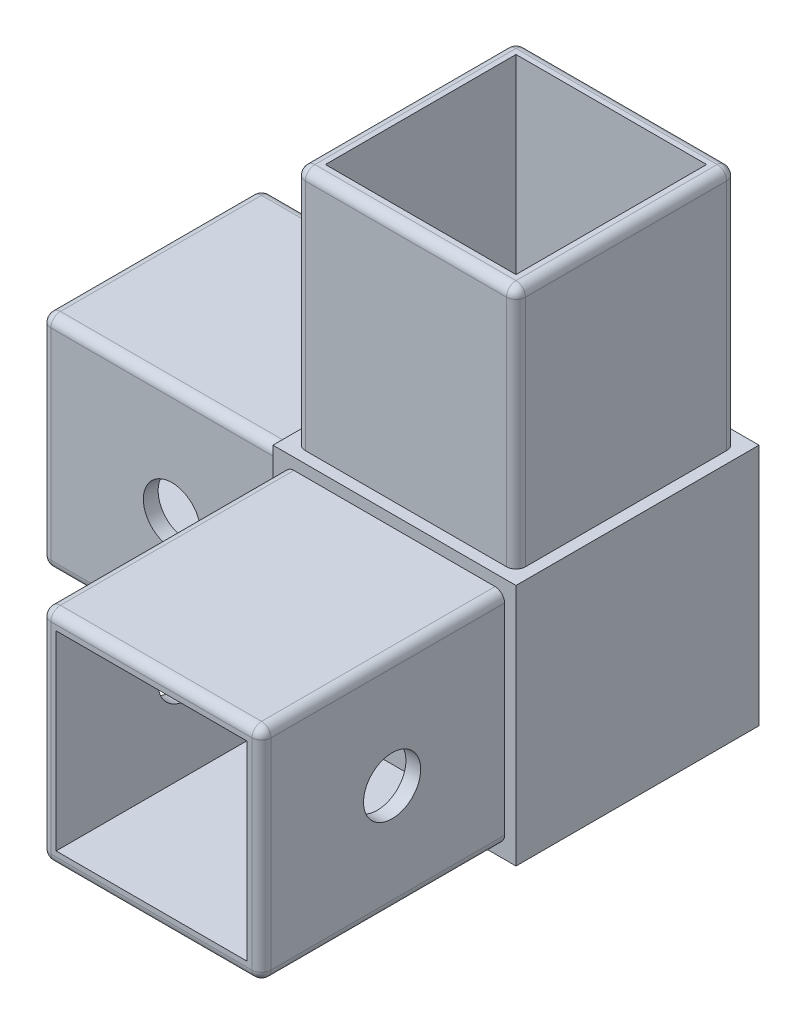
SolidWorks part; units mm, degrees
material "PBT General Purpose"
ref_plane "Front Plane" through (0, 0, 0) normal (0, 0, 1) x (1, 0, 0)
ref_plane "Top Plane" through (0, 0, 0) normal (0, 1, 0) x (1, 0, 0)
ref_plane "Right Plane" through (0, 0, 0) normal (1, 0, 0) x (0, 0, -1)
sketch "Sketch1" plane through (0, 0, 0) normal (0, 0, 1) x (1, 0, 0)
  line L1 (-12.75, -12.75) -> (12.75, -12.75)
  line L2 (-12.75, -12.75) -> (-12.75, 12.75)
  line L3 (-12.75, 12.75) -> (12.75, 12.75)
  line L4 (12.75, -12.75) -> (12.75, 12.75)
  line L5 (-12.75, -12.75) -> (12.75, 12.75) construction
  line L6 (-12.75, 12.75) -> (12.75, -12.75) construction
  point P0 (0, 0)
  dimension "D1" = 25.5
extrude "Boss-Extrude1" add sketch "Sketch1" along normal blind 25.5
sketch "Sketch2" plane through (0, 12.75, 0) normal (0, 1, 0) x (1, 0, 0)
  line L0 (0, 0) -> (0, -25.5) construction
  line L1 (12.75, -25.5) -> (-12.75, -25.5) construction
  line L3 (12.75, -25.5) -> (12.75, 0) construction
  line L4 (12.75, -12.75) -> (-12.75, -12.75) construction
  line L5 (-12.75, -25.5) -> (-12.75, 0) construction
  line L6 (-11.55, -24.3) -> (11.55, -24.3)
  line L7 (-11.55, -24.3) -> (-11.55, -1.2)
  line L8 (-11.55, -1.2) -> (11.55, -1.2)
  line L9 (11.55, -24.3) -> (11.55, -1.2)
  line L10 (-11.55, -24.3) -> (11.55, -1.2) construction
  line L11 (-11.55, -1.2) -> (11.55, -24.3) construction
  line L12 (-10, -2.75) -> (10, -2.75)
  line L13 (-10, -2.75) -> (-10, -22.75)
  line L14 (-10, -22.75) -> (10, -22.75)
  line L15 (10, -2.75) -> (10, -22.75)
  line L16 (-10, -2.75) -> (10, -22.75) construction
  line L17 (-10, -22.75) -> (10, -2.75) construction
  point P5 (0, -12.75)
  point P16 (0, -12.75)
  dimension "D1" = 23.1
  dimension "D2" = 20
extrude "Boss-Extrude2" add sketch "Sketch2" along normal blind 25.5
sketch "Sketch3" plane through (0, 0, 25.5) normal (0, 0, 1) x (1, 0, 0)
  line L0 (12.75, 0) -> (-12.75, 0) construction
  line L1 (12.75, -12.75) -> (12.75, 12.75) construction
  line L2 (-12.75, 12.75) -> (-12.75, -12.75) construction
  line L4 (-12.75, -12.75) -> (12.75, -12.75) construction
  line L5 (0, -12.75) -> (0, 12.75) construction
  line L6 (-11.55, 12.75) -> (11.55, 12.75) construction
  line L7 (-11.55, 11.55) -> (11.55, 11.55)
  line L8 (-11.55, 11.55) -> (-11.55, -11.55)
  line L9 (-11.55, -11.55) -> (11.55, -11.55)
  line L10 (11.55, 11.55) -> (11.55, -11.55)
  line L11 (-11.55, 11.55) -> (11.55, -11.55) construction
  line L12 (-11.55, -11.55) -> (11.55, 11.55) construction
  line L13 (-10, -10) -> (10, -10)
  line L14 (-10, -10) -> (-10, 10)
  line L15 (-10, 10) -> (10, 10)
  line L16 (10, -10) -> (10, 10)
  line L17 (-10, -10) -> (10, 10) construction
  line L18 (-10, 10) -> (10, -10) construction
  point P6 (0, 0)
  point P18 (0, 0)
  dimension "D1" = 23.1
  dimension "D2" = 20
extrude "Boss-Extrude3" add sketch "Sketch3" along normal blind 25.5
sketch "Sketch4" plane through (-12.75, 0, 0) normal (-1, 0, 0) x (0, 0, 1)
  line L0 (12.75, 12.75) -> (12.75, -12.75) construction
  line L1 (25.5, 12.75) -> (0, 12.75) construction
  line L2 (25.5, -12.75) -> (0, -12.75) construction
  line L4 (0, 0) -> (25.5, 0) construction
  line L5 (25.5, 11.55) -> (25.5, -11.55) construction
  line L6 (1.2, -11.55) -> (24.3, -11.55)
  line L7 (1.2, -11.55) -> (1.2, 11.55)
  line L8 (1.2, 11.55) -> (24.3, 11.55)
  line L9 (24.3, -11.55) -> (24.3, 11.55)
  line L10 (1.2, -11.55) -> (24.3, 11.55) construction
  line L11 (1.2, 11.55) -> (24.3, -11.55) construction
  line L12 (2.75, -10) -> (22.75, -10)
  line L13 (2.75, -10) -> (2.75, 10)
  line L14 (2.75, 10) -> (22.75, 10)
  line L15 (22.75, -10) -> (22.75, 10)
  line L16 (2.75, -10) -> (22.75, 10) construction
  line L17 (2.75, 10) -> (22.75, -10) construction
  point P6 (12.75, 0)
  point P16 (12.75, 0)
  dimension "D1" = 23.1
  dimension "D2" = 20
extrude "Boss-Extrude4" add sketch "Sketch4" along normal blind 25.5
fillet "Fillet4" radius 1 24 edges at (-11.55, 25.5, 24.3) (-11.55, 25.5, 1.2) (11.55, 25.5, 1.2) (11.55, 25.5, 24.3) (11.55, -11.55, 38.25) (-11.55, -11.55, 38.25) (11.55, 11.55, 38.25) (-11.55, 11.55, 38.25) (-25.5, -11.55, 24.3) (-25.5, -11.55, 1.2) (-25.5, 11.55, 1.2) (-25.5, 11.55, 24.3) (-38.25, 0, 24.3) (-38.25, 0, 1.2) (-38.25, -11.55, 12.75) (-38.25, 11.55, 12.75) (11.55, 0, 51) (0, -11.55, 51) (-11.55, 0, 51) (0, 11.55, 51) (0, 38.25, 1.2) (-11.55, 38.25, 12.75) (0, 38.25, 24.3) (11.55, 38.25, 12.75)
hole_wizard "Ø6.0 (6) Diameter Hole1" positions "Sketch5" profile "Sketch6" hole size "Ø6.0" standard "ANSI Metric" end condition through all
sketch "Sketch5" plane through (0, 0, 1.2) normal (0, 0, -1) x (-1, 0, 0)
  point P0 (24.55, -0.15)
sketch "Sketch6" plane through (-24.55, -0.15, 1.2) normal (1, 0, 0) x (0, 1, 0)
  line L0 (0, 0) -> (0, 49.8)
  line L1 (0, 49.8) -> (3, 49.8)
  line L2 (3, 49.8) -> (3, 0)
  line L5 (3, 0) -> (0, 0)
  line L11 (0, -6.35) -> (0, 107.95) construction
  dimension "Thru Hole Dia." = 6
  dimension "Thru Hole Depth" = 49.8
hole_wizard "Ø6.0 (6) Diameter Hole2" positions "Sketch7" profile "Sketch8" hole size "Ø6.0" standard "ANSI Metric" end condition through all
sketch "Sketch7" plane through (11.55, 0, 0) normal (1, 0, 0) x (0, 0, -1)
  point P0 (-37.3, -0.15)
sketch "Sketch8" plane through (11.55, -0.15, 37.3) normal (0, 1, 0) x (0, 0, -1)
  line L0 (0, 0) -> (0, 49.8)
  line L1 (0, 49.8) -> (3, 49.8)
  line L2 (3, 49.8) -> (3, 0)
  line L5 (3, 0) -> (0, 0)
  line L11 (0, -6.35) -> (0, 107.95) construction
  dimension "Thru Hole Dia." = 6
  dimension "Thru Hole Depth" = 49.8
